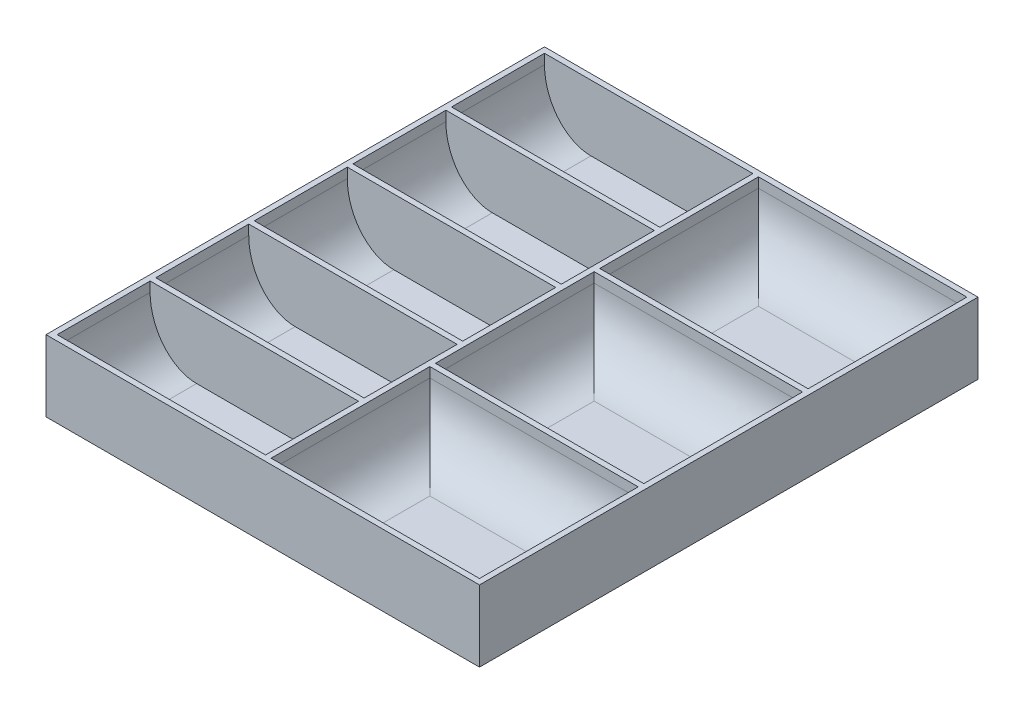
SolidWorks part; units mm, degrees
note: The reader was unsure of these and kept them because the rebuilt part matched: shared geometry of "Sketch1<6>".
ref_plane "Front Plane" through (0, 0, 0) normal (0, 0, 1) x (1, 0, 0)
ref_plane "Top Plane" through (0, 0, 0) normal (0, 1, 0) x (1, 0, 0)
ref_plane "Right Plane" through (0, 0, 0) normal (1, 0, 0) x (0, 0, -1)
sketch "Sketch1" plane through (0, 0, 0) normal (0, 1, 0) x (1, 0, 0)
  line L53 (0, 0) -> (140, 0)
  line L54 (0, 0) -> (0, 161)
  line L55 (0, 161) -> (140, 161)
  line L56 (140, 0) -> (140, 161)
  line L57 (1.8, 31.84) -> (69.1, 31.84)
  line L58 (1.8, 31.84) -> (1.8, 1.8)
  line L59 (1.8, 1.8) -> (69.1, 1.8)
  line L60 (69.1, 31.84) -> (69.1, 1.8)
  line L61 (1.8, 159.2) -> (69.1, 159.2)
  line L62 (1.8, 159.2) -> (1.8, 129.16)
  line L63 (1.8, 129.16) -> (69.1, 129.16)
  line L64 (69.1, 159.2) -> (69.1, 129.16)
  line L65 (138.2, 1.8) -> (70.9, 1.8)
  line L66 (138.2, 1.8) -> (138.2, 53.0667)
  line L67 (138.2, 53.0667) -> (70.9, 53.0667)
  line L68 (70.9, 1.8) -> (70.9, 53.0667)
  line L69 (138.2, 54.8667) -> (70.9, 54.8667)
  line L70 (138.2, 54.8667) -> (138.2, 106.1333)
  line L71 (138.2, 106.1333) -> (70.9, 106.1333)
  line L72 (70.9, 54.8667) -> (70.9, 106.1333)
  line L73 (138.2, 107.9333) -> (70.9, 107.9333)
  line L74 (138.2, 107.9333) -> (138.2, 159.2)
  line L75 (138.2, 159.2) -> (70.9, 159.2)
  line L76 (70.9, 107.9333) -> (70.9, 159.2)
  line L77 (1.8, 33.64) -> (69.1, 33.64)
  line L78 (1.8, 33.64) -> (1.8, 63.68)
  line L79 (1.8, 63.68) -> (69.1, 63.68)
  line L80 (69.1, 33.64) -> (69.1, 63.68)
  line L81 (69.1, 65.48) -> (1.8, 65.48)
  line L82 (69.1, 65.48) -> (69.1, 95.52)
  line L83 (69.1, 95.52) -> (1.8, 95.52)
  line L84 (1.8, 65.48) -> (1.8, 95.52)
  line L85 (1.8, 97.32) -> (69.1, 97.32)
  line L86 (1.8, 97.32) -> (1.8, 127.36)
  line L87 (1.8, 127.36) -> (69.1, 127.36)
  line L88 (69.1, 97.32) -> (69.1, 127.36)
  point P4 (1.8, 16.82)
  point P25 (70.9, 27.4333)
  dimension "D1" = 140
  dimension "D2" = 161
  dimension "D3" = 1.8
  dimension "D7" = 1.8
  dimension "D4" = 1.8
  dimension "D5" = 1.8
  dimension "D9" = 1.8
  dimension "D10" = 1.8
  dimension "D8" = 1.8
  dimension "D6" = 1.8
  dimension "D11" = 1.8
  dimension "D12" = 1.8
  dimension "D13" = 1.8
extrude "Boss-Extrude1" add sketch "Sketch1" against normal blind 1.8 contours L53 L56 L55 L54 L57 L60 L59 L58 L61 L64 L63 L62 | L60 L57 L58 L59 | L68 L65 L66 L67 | L72 L69 L70 L71 | L76 L73 L74 L75 | L77 L80 L79 L78 | L84 L81 L82 L83 | L85 L88 L87 L86
extrude "Boss-Extrude2" add sketch "Sketch1<6>" along normal blind 21.2
sketch "Sketch1<6>" plane through (0, 0, 0) normal (0, 1, 0) x (1, 0, 0) same geometry as "Sketch1"
fillet "Fillet1" radius 18 2 edges at (1.8, 0, -16.82) (35.45, 0, -1.8)
fillet "Fillet2" radius 18 2 edges at (1.8, 0, -48.66) (35.45, 0, -33.64)
fillet "Fillet3" radius 18 2 edges at (35.45, 0, -65.48) (1.8, 0, -80.5)
fillet "Fillet4" radius 18 2 edges at (1.8, 0, -112.34) (35.45, 0, -97.32)
fillet "Fillet5" radius 18 2 edges at (1.8, 0, -144.18) (35.45, 0, -129.16)
fillet "Fillet6" radius 18 2 edges at (69.1, 0, -16.82)
fillet "Fillet7" radius 18 2 edges at (69.1, 0, -48.66)
fillet "Fillet8" radius 18 2 edges at (69.1, 0, -80.5)
fillet "Fillet9" radius 18 2 edges at (69.1, 0, -112.34)
fillet "Fillet10" radius 18 2 edges at (69.1, 0, -144.18)
fillet "Fillet11" radius 18 4 edges at (104.55, 0, -1.8) (138.2, 0, -27.4333) (104.55, 0, -53.0667) (70.9, 0, -27.4333)
fillet "Fillet12" radius 18 4 edges at (104.55, 0, -54.8667) (138.2, 0, -80.5) (104.55, 0, -106.1333) (70.9, 0, -80.5)
fillet "Fillet13" radius 18 4 edges at (104.55, 0, -107.9333) (138.2, 0, -133.5667) (104.55, 0, -159.2) (70.9, 0, -133.5667)
equation "\"padding\"= 1.8"
equation "\"D3@Sketch1\"=\"padding\""
equation "\"D7@Sketch1\"=\"padding\""
equation "\"D1@Boss-Extrude1\"=\"padding\""
equation "\"D4@Sketch1\"=\"padding\""
equation "\"D5@Sketch1\"=\"padding\""
equation "\"D9@Sketch1\"=\"padding\""
equation "\"D10@Sketch1\"=\"padding\""
equation "\"D8@Sketch1\"=\"padding\""
equation "\"D6@Sketch1\"=\"padding\""
equation "\"D11@Sketch1\"=\"padding\""
equation "\"D12@Sketch1\"=\"padding\""
equation "\"D13@Sketch1\"=\"padding\""
equation "\"`8\"=20"
